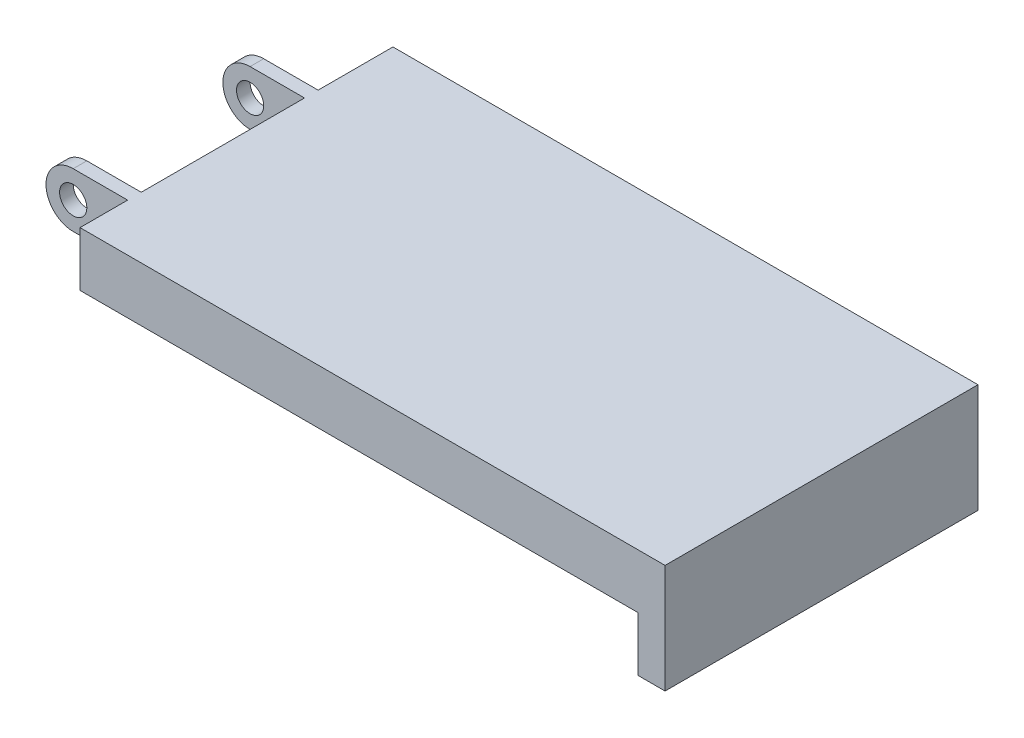
SolidWorks part; units mm, degrees
note: The reader was unsure of these and kept them because the rebuilt part matched: shared geometry of "草图3<2>".
ref_plane "前视基准面" through (0, 0, 0) normal (0, 0, 1) x (1, 0, 0)
ref_plane "上视基准面" through (0, 0, 0) normal (0, 1, 0) x (1, 0, 0)
ref_plane "右视基准面" through (0, 0, 0) normal (1, 0, 0) x (0, 0, -1)
sketch "草图1" plane through (0, 0, 0) normal (0, 0, 1) x (1, 0, 0)
  line L0 (0, 2) -> (47, 2)
  line L1 (47, 2) -> (47, -6)
  line L2 (47, -6) -> (45, -6)
  line L3 (45, -6) -> (45, -2)
  line L4 (45, -2) -> (0, -2)
  circle A0 centre (0, 0) radius 1
  arc A1 (0, 2) -> (0, -2) centre (0, 0) ccw
extrude "凸台-拉伸1" add sketch "草图1" along normal blind 24
sketch "草图2" plane through (0, 0, 24) normal (0, 0, 1) x (1, 0, 0)
  line L0 (4, -2) -> (4, 2)
  line L1 (47, 2) -> (0, 2) construction
  line L2 (4, 2) -> (-4, 2)
  line L3 (-4, 2) -> (-4, -2)
  line L4 (-4, -2) -> (4, -2)
extrude "切除-拉伸2" cut sketch "草图2" against normal blind 4
sketch "草图3" plane through (0, 0, 0) normal (0, 0, -1) x (-1, 0, 0)
  line L0 (0, 2) -> (-4, 2)
  line L1 (-47, 2) -> (0, 2) construction
  line L2 (-4, 2) -> (-4, -2)
  line L3 (0, -2) -> (-45, -2) construction
  line L4 (-4, -2) -> (0, -2)
  line L5 (0, 2) -> (-47, 2)
  line L6 (-47, 2) -> (-47, -6)
  line L7 (-47, -6) -> (-45, -6)
  line L8 (-45, -6) -> (-45, -2)
  line L9 (-45, -2) -> (0, -2)
  arc A1 (0, -2) -> (0, 2) centre (0, 0) ccw
  arc A2 (0, -2) -> (0, 2) centre (0, 0) ccw
  dimension "D1" = 0
extrude "切除-拉伸3" cut sketch "草图3" against normal blind 6
extrude "切除-拉伸4" cut sketch "草图3<2>" against normal blind 12 from offset 7 offset against normal yes
sketch "草图3<2>" plane through (0, 0, 0) normal (0, 0, -1) x (-1, 0, 0) same geometry as "草图3"
sketch "草图4" plane through (45, 0, 0) normal (-1, 0, 0) x (0, 0, 1)
  line L0 (13, -6) -> (13, -5)
  line L2 (11, -5) -> (13, -5)
  line L3 (11, -6) -> (11, -5)
  line L4 (11, -6) -> (13, -6)
extrude "凸台-拉伸2" add sketch "草图4" along normal blind 0.5
sketch "草图5" plane through (0, 0, 0) normal (0, 0, 1) x (1, 0, 0)
  line L0 (4, 2) -> (4, -2)
  line L1 (4, -2) -> (45, -2)
  line L2 (45, -2) -> (45, -6)
  line L3 (45, -6) -> (47, -6)
  line L4 (47, -6) -> (47, 2)
  line L5 (47, 2) -> (4, 2)
extrude "切除-拉伸21" cut sketch "草图5" along normal blind 0.5
sketch "草图6" plane through (0, 0, 24) normal (0, 0, 1) x (1, 0, 0)
  line L0 (4, -2) -> (45, -2)
  line L1 (45, -2) -> (45, -6)
  line L2 (45, -6) -> (47, -6)
  line L3 (45, -6) -> (47, -6) construction
  line L4 (47, -6) -> (47, 2)
  line L5 (47, 2) -> (4, 2)
  line L6 (4, 2) -> (4, -2)
extrude "切除-拉伸22" cut sketch "草图6" against normal blind 0.5
